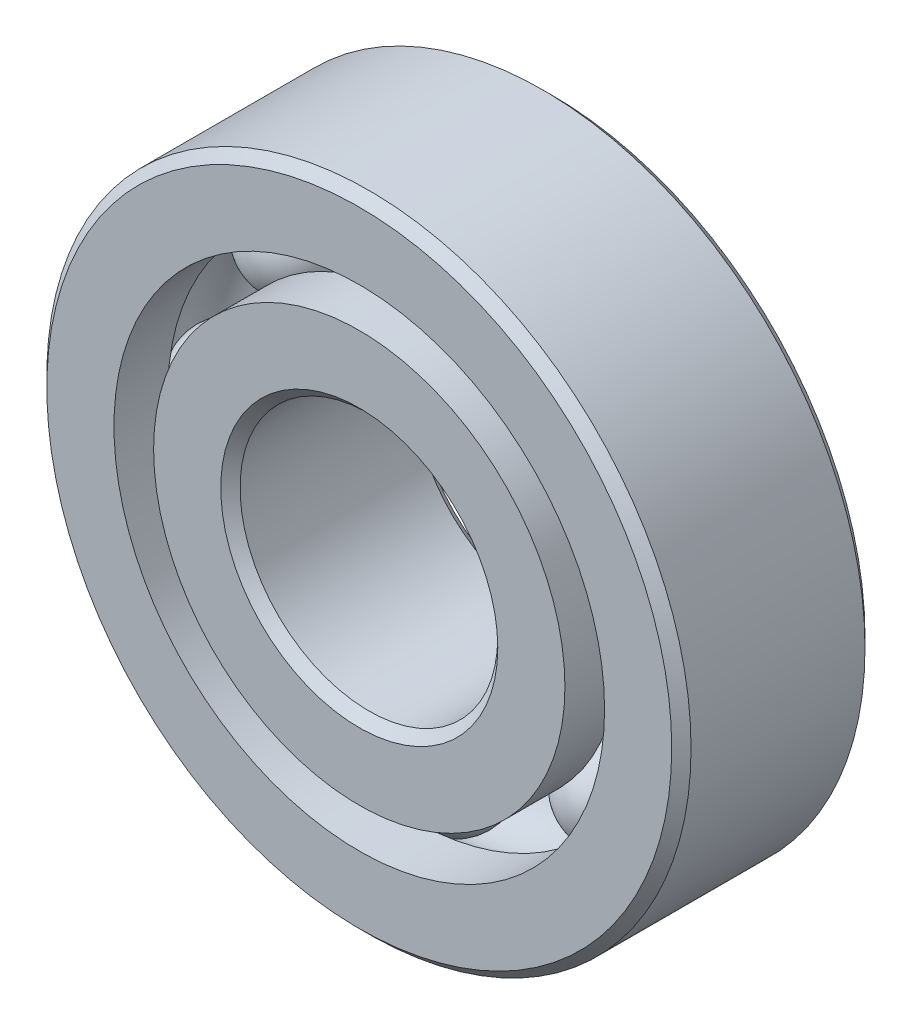
SolidWorks part; units mm, degrees
ref_plane "Front Plane" through (0, 0, 0) normal (0, 0, 1) x (1, 0, 0)
ref_plane "Top Plane" through (0, 0, 0) normal (0, 1, 0) x (1, 0, 0)
ref_plane "Right Plane" through (0, 0, 0) normal (1, 0, 0) x (0, 0, -1)
sketch "Sketch1" plane through (0, 0, 0) normal (1, 0, 0) x (0, 0, -1)
  line L0 (-2.3812, 0) -> (2.3812, 0) construction
  line L1 (0, 7.9375) -> (0, -7.9375) construction
  line L2 (2.1431, 7.9375) -> (-2.1431, 7.9375)
  line L3 (-2.1431, 7.9375) -> (-2.3813, 7.6994)
  line L4 (-2.3813, 7.6994) -> (-2.3813, 6.0447)
  line L5 (-2.3813, 6.0447) -> (-1.0583, 6.0447)
  line L6 (2.3813, 6.0447) -> (1.0583, 6.0447)
  line L7 (2.3813, 7.6994) -> (2.3813, 6.0447)
  line L8 (2.1431, 7.9375) -> (2.3813, 7.6994)
  line L9 (0, 7.9375) -> (0, 5.5562) construction
  line L10 (0, 5.5562) -> (0, 3.175) construction
  arc A0 (-1.0583, 6.0447) -> (1.0583, 6.0447) centre (0, 5.5562) cw
  point P14 (0, 3.175)
  dimension "Width" = 4.7625
  dimension "OD" = 15.875
  dimension "D1" = 45
  dimension "D2" = 0.2381
  dimension "Shaft Dia" = 6.35
  dimension "D3" = 2.1167
  dimension "D4" = 0.4885
revolve "Revolve1" add sketch "Sketch1" angle 360 about L0
sketch "Sketch3" plane through (0, 0, 0) normal (1, 0, 0) x (0, 0, -1)
  line L0 (-2.3813, 5.0678) -> (-1.0583, 5.0678)
  line L1 (0, 7.9375) -> (0, -7.9375) construction
  line L2 (-2.3813, 7.6994) -> (-2.3813, 6.0447) construction
  line L3 (-2.3813, 5.0678) -> (-2.3813, 3.4131)
  line L4 (-2.1431, 7.9375) -> (-2.3813, 7.6994) construction
  line L5 (-2.3813, 3.4131) -> (-2.1431, 3.175)
  line L6 (-2.1431, 3.175) -> (2.1431, 3.175)
  line L7 (2.1431, 7.9375) -> (2.1431, -7.9375) construction
  line L8 (2.1431, 3.175) -> (2.3813, 3.4131)
  line L9 (2.3813, -7.6994) -> (2.3813, 7.6994) construction
  line L10 (2.3813, 3.4131) -> (2.3813, 5.0678)
  line L11 (2.3813, 5.0678) -> (1.0583, 5.0678)
  line L13 (2.1431, 7.9375) -> (2.3813, 7.6994) construction
  arc A0 (1.0583, 6.0447) -> (-1.0583, 6.0447) centre (0, 5.5562) ccw construction
  arc A1 (1.0583, 5.0678) -> (-1.0583, 5.0678) centre (0, 5.5562) cw
revolve "Revolve3" add sketch "Sketch3" angle 360 about L0
sketch "Sketch4" plane through (0, 0, 0) normal (1, 0, 0) x (0, 0, -1)
  line L0 (-1.1656, 5.5562) -> (1.1656, 5.5562)
  arc A2 (-1.1656, 5.5562) -> (1.1656, 5.5562) centre (0, 5.5562) cw
  arc A3 (1.0583, 6.0447) -> (-1.0583, 6.0447) centre (0, 5.5562) ccw construction
revolve "Revolve4" add sketch "Sketch4" angle 360 about L0
ref_axis "Axis1" through (0, 0, -2.3812) along (0, 0, 1)
pattern_circular "CirPattern1" count 8 every 45 about axis through (0, 0, -2.3812) along (0, 0, 1) of bodies 104
sketch "Sketch5" plane through (0, 0, 0) normal (1, 0, 0) x (0, 0, -1)
  line L0 (-2.3813, 6.0447) -> (-1.0583, 6.0447) construction
  line L1 (-2.2622, 6.0447) -> (-1.1656, 6.0447)
  line L2 (-2.2622, 6.0447) -> (-2.2622, 5.0678)
  line L3 (-2.2622, 5.0678) -> (-1.1656, 5.0678)
  line L4 (-1.1656, 6.0447) -> (-1.1656, 5.0678)
  line L5 (-2.3813, 5.0678) -> (-1.0583, 5.0678) construction
  line L6 (2.3813, 6.0447) -> (1.0583, 6.0447) construction
  line L7 (2.2622, 6.0447) -> (1.1656, 6.0447)
  line L8 (2.2622, 6.0447) -> (2.2622, 5.0678)
  line L9 (2.2622, 5.0678) -> (1.1656, 5.0678)
  line L10 (1.1656, 6.0447) -> (1.1656, 5.0678)
  line L11 (2.3813, 5.0678) -> (1.0583, 5.0678) construction
  line L12 (-2.1431, 7.9375) -> (-2.3813, 7.6994) construction
  point P18 (-2.2622, 7.8184)
revolve "Revolve5" [suppressed] add sketch "Sketch5" angle 360 about L0
equation "\"D2@Sketch1\" = \"Width@Sketch1\"*.05"
equation "\"D3@Sketch1\" = \"Width@Sketch1\"/2.25"
equation "\"D4@Sketch1\" = (((\"OD@Sketch1\"-\"Width@Sketch1\")/2)/3.25)/3.5"
equation "\"D2@CirPattern1\" = 360/\"Balls@CirPattern1\""
